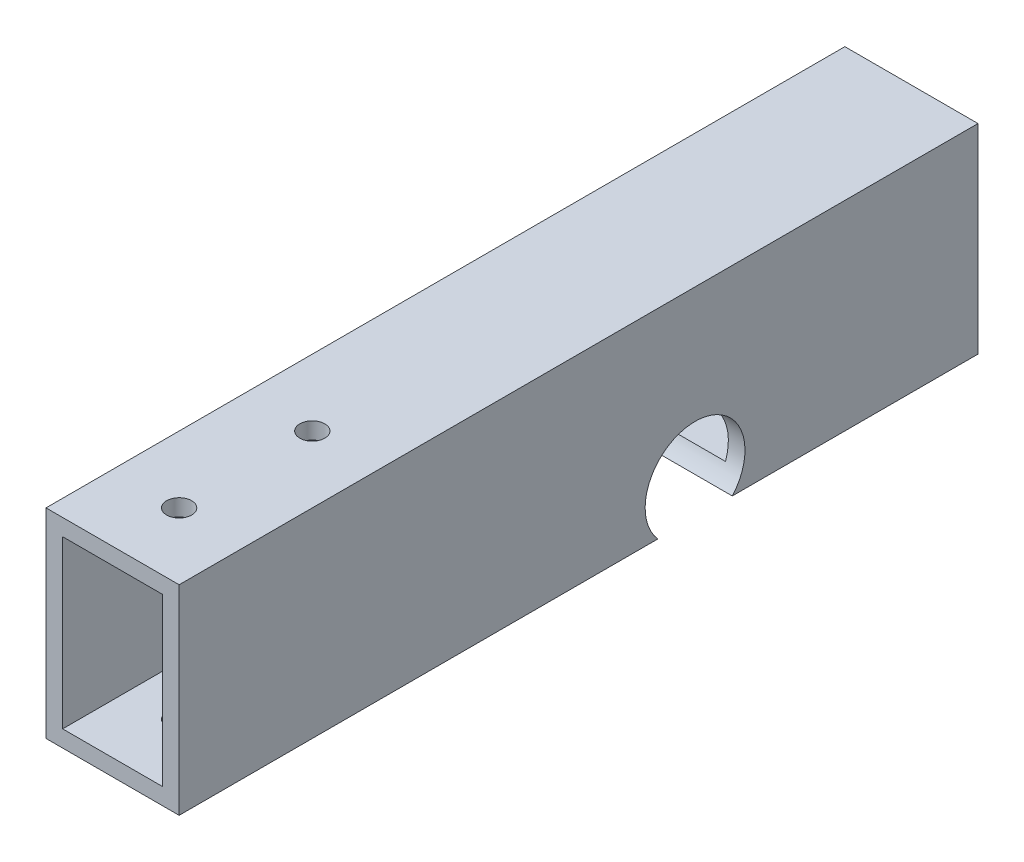
SolidWorks part; units mm, degrees
ref_plane "Front Plane" through (0, 0, 0) normal (0, 0, 1) x (1, 0, 0)
ref_plane "Top Plane" through (0, 0, 0) normal (0, 1, 0) x (1, 0, 0)
ref_plane "Right Plane" through (0, 0, 0) normal (1, 0, 0) x (0, 0, -1)
sketch "Sketch1" plane through (0, 0, 0) normal (0, 0, 1) x (1, 0, 0)
  line L1 (-12.7, 19.05) -> (12.7, 19.05)
  line L2 (-12.7, 19.05) -> (-12.7, -19.05)
  line L3 (-12.7, -19.05) -> (12.7, -19.05)
  line L4 (12.7, 19.05) -> (12.7, -19.05)
  line L5 (-12.7, 19.05) -> (12.7, -19.05) construction
  line L6 (-12.7, -19.05) -> (12.7, 19.05) construction
  point P0 (0, 0)
  dimension "D1" = 25.4
  dimension "D2" = 38.1
extrude "Boss-Extrude1" add sketch "Sketch1" along normal blind 152.4
shell "Shell1" thickness 3.175 removed face at (0, 0, 0) removed face at (0, 0, 152.4)
sketch "Sketch2" plane through (12.7, 0, 0) normal (1, 0, 0) x (0, 0, -1)
  line L0 (-152.4, -19.05) -> (0, -19.05) construction
  line L1 (0, -19.05) -> (0, 19.05) construction
  circle A0 centre (-53.975, -12.7) radius 9.525
  dimension "D1" = 19.05
  dimension "D2" = 6.35
  dimension "D3" = 53.975
extrude "Cut-Extrude1" cut sketch "Sketch2" against normal through all
sketch "Sketch3" plane through (0, 19.05, 0) normal (0, 1, 0) x (1, 0, 0)
  line L0 (12.7, -152.4) -> (-12.7, -152.4) construction
  circle A0 centre (0, -139.7) radius 2.3812
  circle A1 centre (0, -114.3) radius 2.3812
  point P6 (0, 0)
  dimension "D1" = 4.7625
  dimension "D3" = 4.7625
  dimension "D2" = 12.7
  dimension "D4" = 25.4
extrude "Cut-Extrude2" cut sketch "Sketch3" against normal through all
